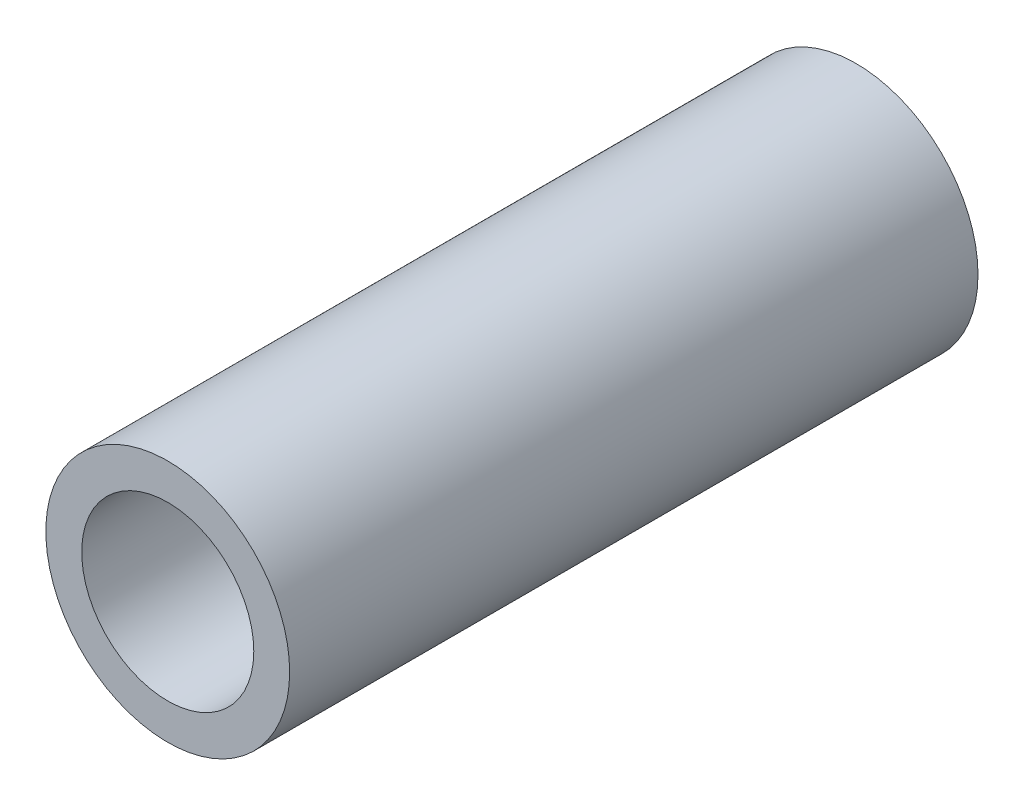
SolidWorks part; units mm, degrees
material "Silicon Rubber"
ref_plane "X-Y Datum" through (0, 0, 0) normal (0, 0, 1) x (1, 0, 0)
ref_plane "X-Z Datum" through (0, 0, 0) normal (0, 1, 0) x (1, 0, 0)
ref_plane "Y-Z Datum" through (0, 0, 0) normal (1, 0, 0) x (0, 0, -1)
sketch3d "3DSketch1"
  line L0 (0, 0, 0) -> (0, 0, 76.2)
  dimension "D1" = 76.2
sweep "Sweep1" add path "3DSketch1" circular profile diameter 26.9875 parameters "D3"=26.9875
sweep "Cut-Sweep1" cut path "3DSketch1<2>" circular profile diameter 19.05 parameters "D3"=19.05
sketch3d "3DSketch1<2>" same geometry as "3DSketch1"
sketch3d "3DSketch2"
  circle A0 centre (0, 0, 50.8) radius 9.525 construction
  circle A1 centre (0, 0, 25.4) radius 9.525 construction
  circle A2 centre (0, 0, 76.2) radius 9.525 construction
  point P4 (0, 0, 15.875)
  point P6 (0, 0, 66.675)
  point P10 (0, 0, 41.275)
  dimension "D1" = 25.4
  dimension "D2" = 25.4
